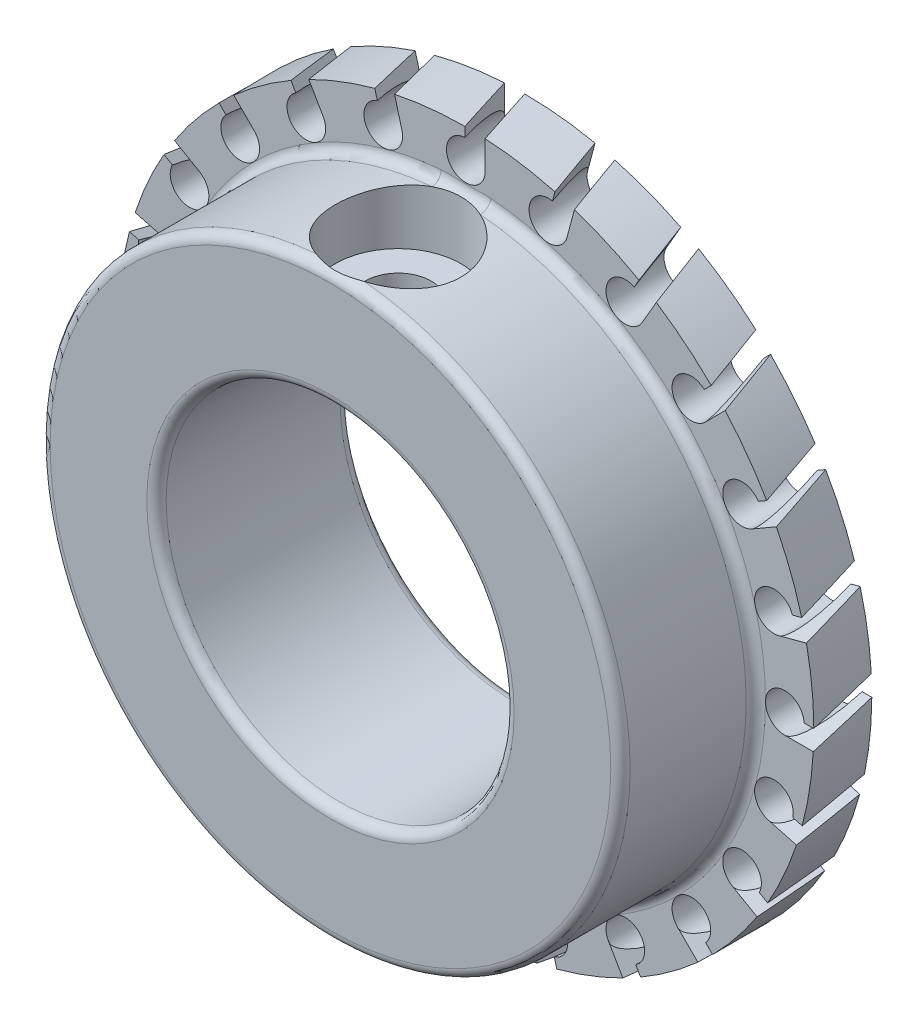
SolidWorks part; units mm, degrees
ref_plane "前基準面" through (0, 0, 0) normal (0, 0, 1) x (1, 0, 0)
ref_plane "上基準面" through (0, 0, 0) normal (0, 1, 0) x (1, 0, 0)
ref_plane "右基準面" through (0, 0, 0) normal (1, 0, 0) x (0, 0, -1)
sketch "草圖8" plane through (0, 0, 0) normal (1, 0, 0) x (0, 0, -1)
  line L0 (-9, 15) -> (7, 15)
  line L1 (7, 15) -> (7, 18)
  line L2 (7, 18) -> (10, 18)
  line L3 (10, 18) -> (10, 9)
  line L7 (-9, 9) -> (-9, 15)
  line L8 (-9, 9) -> (10, 9)
  line L9 (-9, 0) -> (0, 0) construction
  dimension "D1" = 3
  dimension "D2" = 19
  dimension "D3" = 15
  dimension "D4" = 9
  dimension "D5" = 18
  dimension "D6" = 7
revolve "旋轉1" add sketch "草圖8" angle 360 about L9
sketch "草圖9" plane through (0, 0, -10) normal (0, 0, -1) x (-1, 0, 0)
  line L0 (0, 0) -> (0, 18) construction
  circle A0 centre (0, 16.5) radius 1
  circle A1 centre (0, 0) radius 18 construction
  dimension "D1" = 1.5
  dimension "D2" = 2
extrude "除料-伸長2" cut sketch "草圖9" against normal through all both and the other way through all contours A0
ref_plane "平面3" through (0, 16.5, 0) normal (0, 1, 0) x (1, 0, 0)
sketch "草圖10" plane through (0, 16.5, 0) normal (0, 1, 0) x (1, 0, 0)
  line L4 (-1, 7) -> (1, 7) construction
  line L5 (1, 10) -> (-1, 10) construction
  line L6 (-1.317, 11) -> (-0.3637, 11.3022)
  line L7 (-1.317, 11) -> (0.3637, 5.6978)
  line L8 (-0.3637, 11.3022) -> (1.317, 6)
  line L9 (0.3637, 5.6978) -> (1.317, 6)
  line L10 (-1, 7) -> (1, 7) construction
  line L11 (1, 10) -> (-1, 10) construction
  dimension "D1" = 1
  dimension "D2" = 1
  dimension "D3" = 1
extrude "除料-伸長5" cut sketch "草圖10" along normal blind 10 contours L6 L8 L9 L7
pattern_circular "環狀複製排列3" count 24 over 360 about axis through (0, 0, 9) along (0, 0, 1) of "除料-伸長5", "除料-伸長2"
sketch "草圖11" plane through (0, 0, 0) normal (0, 0, 1) x (1, 0, 0)
  line L0 (14.3, 0.7558) -> (14.3, -0.7558)
  line L1 (13.1861, 1.5223) -> (13.8479, 1.345)
  line L2 (13.1861, -1.5223) -> (13.8479, -1.345)
  line L3 (-14.3, -0.7558) -> (-14.3, 0.7558)
  line L4 (-13.1861, -1.5223) -> (-13.8479, -1.345)
  line L5 (-13.1861, 1.5223) -> (-13.8479, 1.345)
  line L6 (-13.6961, 4.1807) -> (-13.1791, 5.6011)
  line L7 (-12.9115, 3.0794) -> (-13.4728, 3.4724)
  line L8 (-11.8702, 5.9404) -> (-12.5527, 6.0001)
  line L9 (13.1791, 5.6011) -> (13.6961, 4.1807)
  line L10 (12.9115, 3.0794) -> (13.4728, 3.4724)
  line L11 (11.8702, 5.9404) -> (12.5527, 6.0001)
  line L12 (-13.1791, -5.6011) -> (-13.6961, -4.1807)
  line L13 (-11.8702, -5.9404) -> (-12.5527, -6.0001)
  line L14 (-12.9115, -3.0794) -> (-13.4728, -3.4724)
  line L15 (13.6961, -4.1807) -> (13.1791, -5.6011)
  line L16 (12.9115, -3.0794) -> (13.4728, -3.4724)
  line L17 (11.8702, -5.9404) -> (12.5527, -6.0001)
  line L18 (-1.7389, -14.214) -> (-3.2274, -13.9515)
  line L19 (-0.7906, -13.2501) -> (-1.0801, -13.8711)
  line L20 (-3.7889, -12.7214) -> (-3.7292, -13.4039)
  line L21 (-3.2274, 13.9515) -> (-1.7389, 14.214)
  line L22 (-3.7889, 12.7214) -> (-3.7292, 13.4039)
  line L23 (-0.7906, 13.2501) -> (-1.0801, 13.8711)
  line L24 (3.2274, -13.9515) -> (1.7389, -14.214)
  line L25 (3.7889, -12.7214) -> (3.7292, -13.4039)
  line L26 (0.7906, -13.2501) -> (1.0801, -13.8711)
  line L27 (1.7389, 14.214) -> (3.2274, 13.9515)
  line L28 (3.7292, 13.4039) -> (3.7889, 12.7214)
  line L29 (1.0801, 13.8711) -> (0.7906, 13.2501)
  line L30 (-6.4955, -12.762) -> (-7.8045, -12.0063)
  line L31 (-5.2747, -12.1806) -> (-5.7592, -12.6651)
  line L32 (-7.9114, -10.6583) -> (-8.0887, -11.3201)
  line L33 (6.4955, 12.762) -> (7.8045, 12.0063)
  line L34 (5.2747, 12.1806) -> (5.7592, 12.6651)
  line L35 (7.9114, 10.6583) -> (8.0887, 11.3201)
  line L36 (-7.8045, 12.0063) -> (-6.4955, 12.762)
  line L37 (-5.2747, 12.1806) -> (-5.7592, 12.6651)
  line L38 (-7.9114, 10.6583) -> (-8.0887, 11.3201)
  line L39 (7.8045, -12.0063) -> (6.4955, -12.762)
  line L40 (5.2747, -12.1806) -> (5.7592, -12.6651)
  line L41 (7.9114, -10.6583) -> (8.0887, -11.3201)
  line L42 (11.4402, -8.6129) -> (10.4686, -9.7708)
  line L43 (9.1226, -9.642) -> (9.7436, -9.9316)
  line L44 (11.0796, -7.3097) -> (11.4726, -7.8709)
  line L45 (-11.4402, 8.6129) -> (-10.4686, 9.7708)
  line L46 (-9.1226, 9.642) -> (-9.7436, 9.9316)
  line L47 (-11.0796, 7.3097) -> (-11.4726, 7.8709)
  line L48 (-10.4686, -9.7708) -> (-11.4402, -8.6129)
  line L49 (-9.1226, -9.642) -> (-9.7436, -9.9316)
  line L50 (-11.0796, -7.3097) -> (-11.4726, -7.8709)
  line L51 (10.4686, 9.7708) -> (11.4402, 8.6129)
  line L52 (9.1226, 9.642) -> (9.7436, 9.9316)
  line L53 (11.0796, 7.3097) -> (11.4726, 7.8709)
  arc A0 (11.2835, 6.2524) -> (11.0565, 6.6456) centre (0, 0) ccw
  arc A1 (-11.2835, -6.2524) -> (-11.0565, -6.6456) centre (0, 0) ccw
  arc A2 (-8.1168, 10.0263) -> (-8.4646, 9.7345) centre (0, 0) ccw
  arc A3 (8.1168, -10.0263) -> (8.4646, -9.7345) centre (0, 0) ccw
  arc A4 (4.1981, -12.1978) -> (4.6247, -12.0425) centre (0, 0) ccw
  arc A5 (-4.1981, 12.1978) -> (-4.6247, 12.0425) centre (0, 0) ccw
  arc A6 (8.4646, 9.7345) -> (8.1168, 10.0263) centre (0, 0) ccw
  arc A7 (-8.4646, -9.7345) -> (-8.1168, -10.0263) centre (0, 0) ccw
  arc A8 (0.227, 12.898) -> (-0.227, 12.898) centre (0, 0) ccw
  arc A9 (-0.227, -12.898) -> (0.227, -12.898) centre (0, 0) ccw
  arc A10 (4.6247, 12.0425) -> (4.1981, 12.1978) centre (0, 0) ccw
  arc A11 (-4.6247, -12.0425) -> (-4.1981, -12.1978) centre (0, 0) ccw
  arc A12 (11.0565, -6.6456) -> (11.2835, -6.2524) centre (0, 0) ccw
  arc A13 (-12.7415, -2.0162) -> (-12.6626, -2.4633) centre (0, 0) ccw
  arc A14 (12.7415, 2.0162) -> (12.6626, 2.4633) centre (0, 0) ccw
  arc A15 (-12.6626, 2.4633) -> (-12.7415, 2.0162) centre (0, 0) ccw
  arc A16 (12.6626, -2.4633) -> (12.7415, -2.0162) centre (0, 0) ccw
  arc A17 (-11.0565, 6.6456) -> (-11.2835, 6.2524) centre (0, 0) ccw
  arc A18 (13.1791, 5.6011) -> (12.5527, 6.0001) centre (12.6059, 5.3924) ccw
  arc A19 (7.8045, -12.0063) -> (8.0887, -11.3201) centre (7.4995, -11.478) ccw
  arc A20 (-1.7389, -14.214) -> (-1.0801, -13.8711) centre (-1.633, -13.6133) ccw
  arc A21 (-0.7906, 13.2501) -> (-0.227, 12.898) centre (-0.2377, 13.5079) ccw
  arc A22 (13.6961, -4.1807) -> (13.4728, -3.4724) centre (13.1229, -3.9721) ccw
  arc A23 (0.227, 12.898) -> (0.7906, 13.2501) centre (0.2377, 13.5079) ccw
  arc A24 (6.4955, 12.762) -> (5.7592, 12.6651) centre (6.1905, 12.2338) ccw
  arc A25 (1.7389, 14.214) -> (1.0801, 13.8711) centre (1.633, 13.6133) ccw
  arc A26 (3.2274, -13.9515) -> (3.7292, -13.4039) centre (3.1215, -13.3508) ccw
  arc A27 (-5.7592, 12.6651) -> (-6.4955, 12.762) centre (-6.1905, 12.2338) ccw
  arc A28 (11.4402, -8.6129) -> (11.4726, -7.8709) centre (10.9729, -8.2208) ccw
  arc A29 (-5.2747, 12.1806) -> (-4.6247, 12.0425) centre (-4.8434, 12.612) ccw
  arc A30 (14.3, 0.7558) -> (13.8479, 1.345) centre (13.69, 0.7558) ccw
  arc A31 (-4.1981, 12.1978) -> (-3.7889, 12.7214) centre (-4.3966, 12.7746) ccw
  arc A32 (10.4686, 9.7708) -> (9.7436, 9.9316) centre (10.0014, 9.3787) ccw
  arc A33 (-3.2274, 13.9515) -> (-3.7292, 13.4039) centre (-3.1215, 13.3508) ccw
  arc A34 (0.7906, -13.2501) -> (0.227, -12.898) centre (0.2377, -13.5079) ccw
  arc A35 (-9.7436, 9.9316) -> (-10.4686, 9.7708) centre (-10.0014, 9.3787) ccw
  arc A36 (5.2747, -12.1806) -> (4.6247, -12.0425) centre (4.8434, -12.612) ccw
  arc A37 (-9.1226, 9.642) -> (-8.4646, 9.7345) centre (-8.8648, 10.1949) ccw
  arc A38 (9.1226, -9.642) -> (8.4646, -9.7345) centre (8.8648, -10.1949) ccw
  arc A39 (-8.1168, 10.0263) -> (-7.9114, 10.6583) centre (-8.5006, 10.5005) ccw
  arc A40 (11.8702, -5.9404) -> (11.2835, -6.2524) centre (11.8171, -6.5481) ccw
  arc A41 (-7.8045, 12.0063) -> (-8.0887, 11.3201) centre (-7.4995, 11.478) ccw
  arc A42 (13.1861, -1.5223) -> (12.7415, -2.0162) centre (13.344, -2.1115) ccw
  arc A43 (-12.5527, 6.0001) -> (-13.1791, 5.6011) centre (-12.6059, 5.3924) ccw
  arc A44 (12.9115, 3.0794) -> (12.6626, 2.4633) centre (13.2614, 2.5797) ccw
  arc A45 (-11.8702, 5.9404) -> (-11.2835, 6.2524) centre (-11.8171, 6.5481) ccw
  arc A46 (11.0796, 7.3097) -> (11.0565, 6.6456) centre (11.5793, 6.9598) ccw
  arc A47 (-11.0565, 6.6456) -> (-11.0796, 7.3097) centre (-11.5793, 6.9598) ccw
  arc A48 (7.9114, 10.6583) -> (8.1168, 10.0263) centre (8.5006, 10.5005) ccw
  arc A49 (-11.4402, 8.6129) -> (-11.4726, 7.8709) centre (-10.9729, 8.2208) ccw
  arc A50 (3.7889, 12.7214) -> (4.1981, 12.1978) centre (4.3966, 12.7746) ccw
  arc A51 (-13.8479, 1.345) -> (-14.3, 0.7558) centre (-13.69, 0.7558) ccw
  arc A52 (1.0801, -13.8711) -> (1.7389, -14.214) centre (1.633, -13.6133) ccw
  arc A53 (-13.1861, 1.5223) -> (-12.7415, 2.0162) centre (-13.344, 2.1115) ccw
  arc A54 (-0.227, -12.898) -> (-0.7906, -13.2501) centre (-0.2377, -13.5079) ccw
  arc A55 (-12.6626, 2.4633) -> (-12.9115, 3.0794) centre (-13.2614, 2.5797) ccw
  arc A56 (5.7592, -12.6651) -> (6.4955, -12.762) centre (6.1905, -12.2338) ccw
  arc A57 (-13.6961, 4.1807) -> (-13.4728, 3.4724) centre (-13.1229, 3.9721) ccw
  arc A58 (4.1981, -12.1978) -> (3.7889, -12.7214) centre (4.3966, -12.7746) ccw
  arc A59 (-13.4728, -3.4724) -> (-13.6961, -4.1807) centre (-13.1229, -3.9721) ccw
  arc A60 (9.7436, -9.9316) -> (10.4686, -9.7708) centre (10.0014, -9.3787) ccw
  arc A61 (-12.9115, -3.0794) -> (-12.6626, -2.4633) centre (-13.2614, -2.5797) ccw
  arc A62 (8.1168, -10.0263) -> (7.9114, -10.6583) centre (8.5006, -10.5005) ccw
  arc A63 (-12.7415, -2.0162) -> (-13.1861, -1.5223) centre (-13.344, -2.1115) ccw
  arc A64 (12.5527, -6.0001) -> (13.1791, -5.6011) centre (12.6059, -5.3924) ccw
  arc A65 (-14.3, -0.7558) -> (-13.8479, -1.345) centre (-13.69, -0.7558) ccw
  arc A66 (11.0565, -6.6456) -> (11.0796, -7.3097) centre (11.5793, -6.9598) ccw
  arc A67 (-11.4726, -7.8709) -> (-11.4402, -8.6129) centre (-10.9729, -8.2208) ccw
  arc A68 (13.8479, -1.345) -> (14.3, -0.7558) centre (13.69, -0.7558) ccw
  arc A69 (-11.0796, -7.3097) -> (-11.0565, -6.6456) centre (-11.5793, -6.9598) ccw
  arc A70 (12.6626, -2.4633) -> (12.9115, -3.0794) centre (13.2614, -2.5797) ccw
  arc A71 (-11.2835, -6.2524) -> (-11.8702, -5.9404) centre (-11.8171, -6.5481) ccw
  arc A72 (13.4728, 3.4724) -> (13.6961, 4.1807) centre (13.1229, 3.9721) ccw
  arc A73 (-13.1791, -5.6011) -> (-12.5527, -6.0001) centre (-12.6059, -5.3924) ccw
  arc A74 (12.7415, 2.0162) -> (13.1861, 1.5223) centre (13.344, 2.1115) ccw
  arc A75 (-8.0887, -11.3201) -> (-7.8045, -12.0063) centre (-7.4995, -11.478) ccw
  arc A76 (11.4726, 7.8709) -> (11.4402, 8.6129) centre (10.9729, 8.2208) ccw
  arc A77 (-7.9114, -10.6583) -> (-8.1168, -10.0263) centre (-8.5006, -10.5005) ccw
  arc A78 (11.2835, 6.2524) -> (11.8702, 5.9404) centre (11.8171, 6.5481) ccw
  arc A79 (-8.4646, -9.7345) -> (-9.1226, -9.642) centre (-8.8648, -10.1949) ccw
  arc A80 (8.0887, 11.3201) -> (7.8045, 12.0063) centre (7.4995, 11.478) ccw
  arc A81 (-10.4686, -9.7708) -> (-9.7436, -9.9316) centre (-10.0014, -9.3787) ccw
  arc A82 (8.4646, 9.7345) -> (9.1226, 9.642) centre (8.8648, 10.1949) ccw
  arc A83 (-3.7292, -13.4039) -> (-3.2274, -13.9515) centre (-3.1215, -13.3508) ccw
  arc A84 (3.7292, 13.4039) -> (3.2274, 13.9515) centre (3.1215, 13.3508) ccw
  arc A85 (-3.7889, -12.7214) -> (-4.1981, -12.1978) centre (-4.3966, -12.7746) ccw
  arc A86 (4.6247, 12.0425) -> (5.2747, 12.1806) centre (4.8434, 12.612) ccw
  arc A87 (-4.6247, -12.0425) -> (-5.2747, -12.1806) centre (-4.8434, -12.612) ccw
  arc A88 (-1.0801, 13.8711) -> (-1.7389, 14.214) centre (-1.633, 13.6133) ccw
  arc A89 (-6.4955, -12.762) -> (-5.7592, -12.6651) centre (-6.1905, -12.2338) ccw
  circle A91 centre (0, 0) radius 15 construction
  circle A92 centre (0, 0) radius 15
extrude "除料-伸長6" cut sketch "草圖11" along normal blind 7
ref_plane "平面4" through (0, 0, -3.5) normal (0, 0, 1) x (1, 0, 0)
sketch "草圖12" plane through (0, 0, -3.5) normal (0, 0, 1) x (1, 0, 0)
  line L0 (-19.1241, 9) -> (-17.3402, 9) construction
  line L1 (-3.25, 21.7168) -> (0, 21.7168)
  line L2 (-3.25, 21.7168) -> (-3.25, 12)
  line L3 (-3.25, 12) -> (-1.7, 12)
  line L4 (0, 21.7168) -> (0, 0)
  line L5 (-1.7, 0) -> (0, 0)
  line L6 (-1.7, 0) -> (-1.7, 12)
  circle A0 centre (0, 0) radius 9 construction
  circle A1 centre (0, 0) radius 9 construction
  point P12 (-3.25, 10.8683)
  dimension "D1" = 3.25
  dimension "D2" = 1.7
  dimension "D3" = 3
revolve "除料-旋轉1" cut sketch "草圖12" angle 360 about L4
sketch "草圖14" plane through (0, 0, 9) normal (0, 0, 1) x (1, 0, 0)
  circle A0 centre (0, 0) radius 15 construction
  circle A1 centre (0, 0) radius 15
extrude "除料-伸長7" cut sketch "草圖14" against normal up to surface (9 mm away) up to face at (15, 0, 0)
fillet "圓角1" radius 0.5 4 edges at (9, 0, 0) (15, 0, 0) (15, 0, -7) (9, 0, -10)
